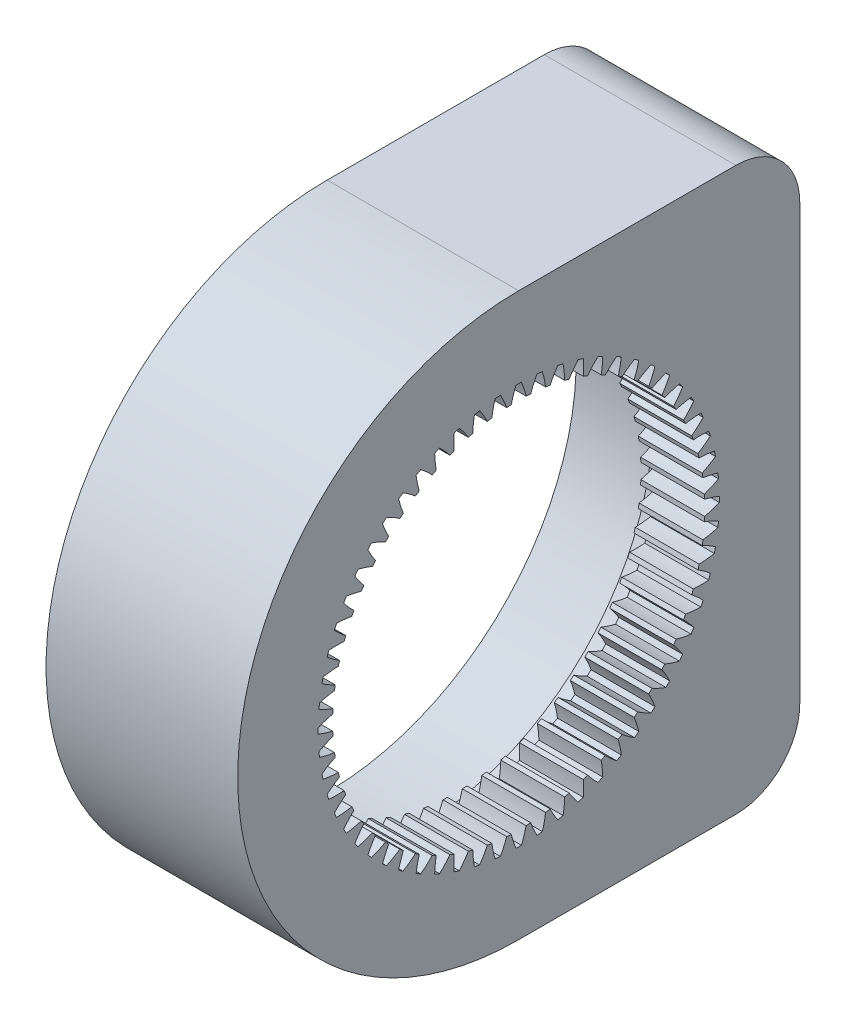
SolidWorks part; units mm, degrees
ref_plane "Plane1" through (0, 0, 0) normal (0, 0, 1) x (1, 0, 0)
ref_plane "Plane2" through (0, 0, 0) normal (0, 1, 0) x (1, 0, 0)
ref_plane "Plane3" through (0, 0, 0) normal (1, 0, 0) x (0, 0, -1)
other "Configuration Table"
sketch "HoldingSke" plane through (0, 0, 0) normal (0, 1, 0) x (1, 0, 0)
  line L0 (0, 0) -> (0.4975, -0.8617)
  line L1 (-15, 0) -> (100, 0) construction
  line L2 (0, 0) -> (-2.1039, 2.3779)
  line L3 (0, 0) -> (-11.863, 4.5341)
  line L4 (0, 0) -> (4.318, 7.479)
  line L5 (0, 0) -> (-23.7986, -8.8762)
  line L6 (0, 0) -> (-10.5278, -7.1032)
  line L7 (-2.1039, 2.3779) -> (3.3635, 27.1825)
  line L8 (-76.2, 3.3829) -> (-54.61, 3.3829)
  line L9 (-67.7845, 28.3722) -> (-49.3413, 33.142)
  line L10 (-76.2, 71.12) -> (104.1128, 71.12)
  line L11 (0, 0) -> (-10, 0)
  line L12 (-76.2, 101.6) -> (-76.162, 101.6)
  line L13 (24.9733, 27.94) -> (52.9518, 28.4284)
  line L14 (24.9733, 27.94) -> (24.9743, 27.94)
  line L15 (24.9733, 27.94) -> (100.4006, 29.5858)
  circle A0 centre (0, 0) radius 44
  circle A1 centre (0, 0) radius 12.7
  circle A2 centre (0, 0) radius 12.7
  dimension "Num_teeth" = 60
  dimension "Pitch_radius" = 180.3128
  dimension "Width" = 10
  dimension "Diameter" = 88
sketch "BasProSke" plane through (0, 0, 0) normal (0, 1, 0) x (1, 0, 0)
  line L0 (-10, 0) -> (60, 0) construction
  line L1 (0, 29.145) -> (0, 44)
  line L2 (0, 29.145) -> (10, 29.145)
  line L3 (10, 29.145) -> (10, 44)
  line L4 (10, 44) -> (0, 44)
  dimension "Thickness" = 10
  dimension "Diameter" = 88
revolve "Base-Revolve" add sketch "BasProSke" angle 360 about L0
sketch "TooCutSke" plane through (0, 0, 0) normal (1, 0, 0) x (0, 0, -1)
  line L3 (0.8842, 30.137) -> (0.8842, 53.6633) construction
  line L4 (0, 0) -> (0, 59.563) construction
  line L5 (0, 0) -> (-3.576, 68.2339) construction
  line L6 (-13.4917, 25.5997) -> (36.416, 28.2152) construction
  circle A0 centre (0, 0) radius 30.15 construction
  circle A1 centre (0, 0) radius 31.4072 construction
  circle A2 centre (0, 0) radius 26.2707 construction
  circle A3 centre (0, 0) radius 29.1196 construction
  arc A4 (1.1722, 29.096) -> (0.4209, 31.4044) centre (-13.4917, 25.5997) ccw
  arc A5 (1.1722, 29.096) -> (-1.1722, 29.096) centre (0, 0) ccw
  arc A6 (0.4209, 31.4044) -> (-0.4209, 31.4044) centre (0, 0) ccw
  arc A7 (-0.4209, 31.4044) -> (-1.1722, 29.096) centre (13.4917, 25.5997) ccw
extrude "ToothCut" cut sketch "TooCutSke" along normal through all
fillet "Breaks" [suppressed] radius 0.1005
fillet "RootFillets" [suppressed] radius 0.2522
pattern_circular "TeethCuts" count 60 every 6 about axis through (-10, 0, 0) along (1, 0, 0) of "RootFillets", "Breaks", "ToothCut"
sketch "Sketch4" plane through (0, 0, 0) normal (-1, 0, 0) x (0, 0, 1)
  circle A0 centre (0, 0) radius 44
  circle A1 centre (0, 0) radius 39
  circle A2 centre (0, 0) radius 44 construction
  dimension "D1" = 78
extrude "Boss-Extrude3" add sketch "Sketch4" along normal blind 20
sketch "Sketch7" plane through (10, 0, 0) normal (1, 0, 0) x (0, 0, -1)
  line L0 (0, 44) -> (44, 44)
  line L1 (44, 44) -> (44, 0)
  circle A0 centre (0, 0) radius 44 construction
  arc A1 (44, 0) -> (0, 44) centre (0, 0) ccw
extrude "Boss-Extrude5" add sketch "Sketch7" against normal up to surface (30 mm away) up to face at (-20, 0, 44)
sketch "Sketch10" plane through (10, 0, 0) normal (1, 0, 0) x (0, 0, -1)
  line L0 (0, -44) -> (44, -44)
  line L1 (44, -44) -> (44, 0)
  line L2 (44, 0) -> (44, 44) construction
  circle A0 centre (0, 0) radius 44 construction
  arc A1 (0, -44) -> (44, 0) centre (0, 0) ccw
  dimension "D1" = 180
extrude "Boss-Extrude6" add sketch "Sketch10" against normal up to surface (30 mm away) up to face at (-20, 11.6291, -11.6291)
fillet "Fillet1" radius 10 2 edges at (-5, 44, -44) (-5, -44, -44)
sketch "Sketch14" plane through (0, 0, 0) normal (-1, 0, 0) x (0, 0, 1)
  circle A0 centre (0, 0) radius 37
  circle A1 centre (0, 0) radius 39 construction
  circle A2 centre (0, 0) radius 39
  dimension "D1" = 2
extrude "Boss-Extrude7" add sketch "Sketch14" along normal blind 6
equation "' \"Module@HoldingSke\" = 6.35"
equation "' \"Num_teeth@HoldingSke\" = 24"
equation "' \"Ap@HoldingSke\" =  14.5"
equation "' \"Ap@HoldingSke\" = 14.5"
equation "' \"Width@HoldingSke\" = 12"
equation "' \"Diameter@HoldingSke\" = 8 * 25.4"
equation "' \"Show_teeth@HoldingSke\" = 100"
equation "' \"Backlash@HoldingSke\" = 0.009 * 25.4"
equation "' \"Addendum_fac@HoldingSke\" = 1.0"
equation "' \"Dedendum_fac@HoldingSke\" = 1.25"
equation "' \"Dedendum_add@HoldingSke\" = 0.00005 * 25.4"
equation "' \"Clearance_fac@HoldingSke\" = 0.25"
equation "\"Pitch@HoldingSke\" = 1 / \"Module@HoldingSke\" "
equation "\"Overcut_dia@TooCutSke\" = (\"Num_teeth@HoldingSke\" - 2 * \"Addendum_fac@HoldingSke\") / \"Pitch@HoldingSke\" - 0.002 * 25.4"
equation "\"Pitch_dia@TooCutSke\" = \"Num_teeth@HoldingSke\" / \"Pitch@HoldingSke\""
equation "\"Base_dia@TooCutSke\" = \"Num_teeth@HoldingSke\" / \"Pitch@HoldingSke\" * cos((\"Ap@HoldingSke\"  * 3.14159265 / 180)) * 0.90"
equation "\"Root_dia@TooCutSke\" = \"Num_teeth@HoldingSke\"  / \"Pitch@HoldingSke\" + 2 *  \"Dedendum_fac@HoldingSke\"/ \"Pitch@HoldingSke\" + \"Dedendum_add@HoldingSke\" * 2"
equation "\"Half_ang@TooCutSke\" = 180 / \"Num_teeth@HoldingSke\""
equation "\"Half_CT@TooCutSke\" = \"Num_teeth@HoldingSke\" / \"Pitch@HoldingSke\" * sin((3.14159265 / 2 / \"Num_teeth@HoldingSke\")) / 2 + 10 * \"Backlash@HoldingSke\" / 4"
equation "\"Flank_rad@TooCutSke\" = \"Num_teeth@HoldingSke\" / \"Pitch@HoldingSke\" / 4"
equation "\"Radius@RootFillets\"= \"Clearance_fac@HoldingSke\" / \"Pitch@HoldingSke\" + \"Dedendum_add@HoldingSke\""
equation "\"Break_rad@Breaks\" = 0.02 / \"Pitch@HoldingSke\" * 5"
equation "\"Num_teeth@TeethCuts\" = int( \"Show_teeth@HoldingSke\" ) + 1"
equation "\"Num_teeth@TeethCuts\" = ((sgn( \"Num_teeth@TeethCuts\" - \"Num_teeth@HoldingSke\" )-1)*( \"Num_teeth@TeethCuts\" - \"Num_teeth@HoldingSke\" ))/-2+ \"Num_teeth@HoldingSke\""
equation "\"Num_teeth@TeethCuts\" = ((sgn( \"Num_teeth@TeethCuts\" - 2.0)+1)*( \"Num_teeth@TeethCuts\" - 2.0))/2 +2.0"
equation "\"Angle@TeethCuts\" = 360.0 / \"Num_teeth@HoldingSke\""
equation "\"Diameter@BasProSke\" = \"Num_teeth@HoldingSke\"  / \"Pitch@HoldingSke\" + 2 *  \"Dedendum_fac@HoldingSke\"/ \"Pitch@HoldingSke\" + \"Dedendum_add@HoldingSke\" * 2 + 0.002 * 25.4"
equation "\"Diameter@BasProSke\" = ((sgn( \"Diameter@BasProSke\"  - \"Diameter@HoldingSke\" )+1)*( \"Diameter@BasProSke\"  - \"Diameter@HoldingSke\" ))/2 + \"Diameter@HoldingSke\""
equation "\"Inside_diameter@BasProSke\" =  (\"Num_teeth@HoldingSke\" - 2 * \"Addendum_fac@HoldingSke\") / \"Pitch@HoldingSke\" "
equation "\"Thickness@BasProSke\"  = \"Width@HoldingSke\""
